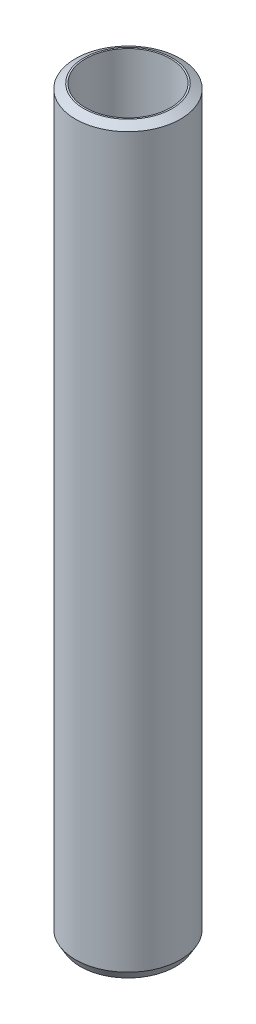
SolidWorks part; units mm, degrees
ref_plane "Front Plane" through (0, 0, 0) normal (0, 0, 1) x (1, 0, 0)
ref_plane "Top Plane" through (0, 0, 0) normal (0, 1, 0) x (1, 0, 0)
ref_plane "Right Plane" through (0, 0, 0) normal (1, 0, 0) x (0, 0, -1)
sketch "Sketch1" plane through (0, 0, 0) normal (0, 1, 0) x (1, 0, 0)
  circle A0 centre (0, 0) radius 42.5
  dimension "SHAFT_OD" = 85
extrude "Boss-Extrude1" add sketch "Sketch1" along normal blind 600
sketch "Sketch2" plane through (0, 0, 0) normal (0, 1, 0) x (1, 0, 0)
  circle A0 centre (0, 0) radius 34.4128
  dimension "BORE_D" = 68.8255
extrude "Cut-Extrude1" cut sketch "Sketch2" along normal through all
chamfer "Chamfer1" distance 3.9448 angle 60 2 edges at (0, 600, 42.5) (0, 0, 42.5) first distance on face at (0, 600, 42.5) first distance on face at (0, 0, 34.4128)
